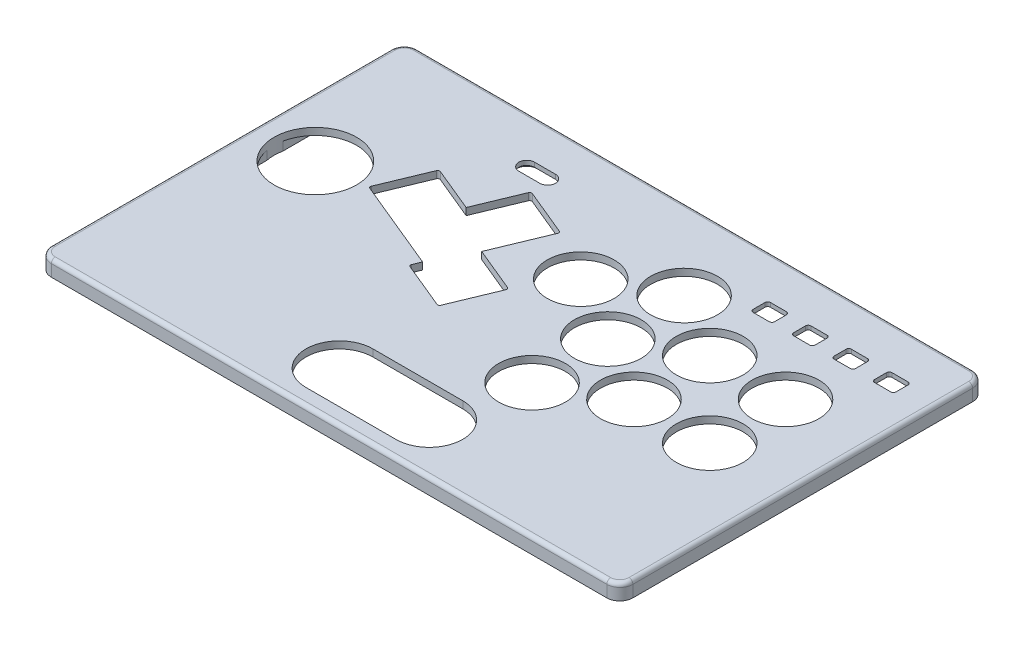
SolidWorks part; units mm, degrees
ref_plane "Front Plane" through (0, 0, 0) normal (0, 0, 1) x (1, 0, 0)
ref_plane "Top Plane" through (0, 0, 0) normal (0, 1, 0) x (1, 0, 0)
ref_plane "Right Plane" through (0, 0, 0) normal (1, 0, 0) x (0, 0, -1)
sketch "Sketch1" plane through (0, 0, 0) normal (0, 1, 0) x (1, 0, 0)
  line L1 (0, 0) -> (222.53, 0)
  line L2 (0, 0) -> (0, 140)
  line L3 (0, 140) -> (222.53, 140)
  line L4 (222.53, 0) -> (222.53, 140)
  line L5 (217.53, 140) -> (50.88, 140) construction
  line L6 (222.53, 5) -> (222.53, 135) construction
extrude "Top Plate" add sketch "Sketch1" along normal blind 6
fillet "Corner Fillet" radius 5 4 edges at (0, 3, -140) (0, 3, 0) (222.53, 3, -140) (222.53, 3, 0)
fillet "Top Fillet" radius 1.5 8 edges at (1.4645, 6, -1.4645) (0, 6, -70) (1.4645, 6, -138.5355) (111.265, 6, -140) (221.0655, 6, -138.5355) (222.53, 6, -70) (221.0655, 6, -1.4645) (111.265, 6, 0)
hole_wizard "M3 Clearance Hole1" positions "3DSketch1" profile "Sketch3" hole size "M3" standard "ANSI Metric"
sketch3d "3DSketch1"
  line L0 (5, 0, 0) -> (217.53, 0, 0) construction
  line L1 (222.53, 0, -5) -> (222.53, 0, -135) construction
  line L2 (217.53, 0, -140) -> (5, 0, -140) construction
  line L3 (0, 0, -135) -> (0, 0, -5) construction
  point P0 (217.03, 0, -5.5)
  point P2 (217.03, 0, -134.5)
  point P4 (5.5, 0, -134.5)
  point P6 (5.5, 0, -5.5)
  dimension "D1" = 5.5
  dimension "D2" = 5.5
  dimension "D3" = 5.5
  dimension "D4" = 5.5
  dimension "D5" = 5.5
  dimension "D6" = 5.5
  dimension "D7" = 5.5
  dimension "D8" = 5.5
sketch "Sketch3" plane through (217.03, 0, -5.5) normal (1, 0, 0) x (0, 0, -1)
  line L0 (0, 0) -> (0, 5.25)
  line L1 (0, 5.25) -> (1.7, 4.2285)
  line L2 (1.7, 4.2285) -> (1.7, 0)
  line L5 (1.7, 0) -> (0, 0)
  line L10 (0, 5.25) -> (-1.7, 4.2285) construction
  line L11 (0, -6.35) -> (0, 107.95) construction
  dimension "Hole Dia." = 3.4
  dimension "Hole Depth" = 5.25
  dimension "Drill Angle" = 118
sketch "Sketch4" plane through (0, 6, 0) normal (0, -1, 0) x (-1, 0, 0)
  line L0 (-94.0588, 59.555) -> (-76.4589, 66.8451) construction
  line L1 (-94.0588, 59.555) -> (-101.349, 77.1549) construction
  line L2 (-76.4589, 66.8451) -> (-77.9897, 70.5406) construction
  line L3 (-101.349, 77.1549) -> (-83.7491, 84.445) construction
  line L4 (-94.0588, 59.555) -> (-83.7491, 84.445) construction
  line L5 (-76.4589, 66.8451) -> (-101.349, 77.1549) construction
  line L6 (-77.9897, 70.5406) -> (-60.3898, 77.8307) construction
  line L7 (-83.7491, 84.445) -> (-85.2798, 88.1405) construction
  line L8 (-60.3898, 77.8307) -> (-67.6799, 95.4306) construction
  line L9 (-85.2798, 88.1405) -> (-67.6799, 95.4306) construction
  line L10 (-77.9897, 70.5406) -> (-67.6799, 95.4306) construction
  line L11 (-60.3898, 77.8307) -> (-85.2798, 88.1405) construction
  line L12 (-60.3898, 77.8307) -> (-42.7899, 85.1209) construction
  line L14 (-42.7899, 85.1209) -> (-50.08, 102.7208) construction
  line L15 (-67.6799, 95.4306) -> (-50.08, 102.7208) construction
  line L16 (-60.3898, 77.8307) -> (-50.08, 102.7208) construction
  line L17 (-42.7899, 85.1209) -> (-67.6799, 95.4306) construction
  line L19 (-67.6799, 95.4306) -> (-74.97, 113.0306) construction
  line L20 (-85.2798, 88.1405) -> (-92.5699, 105.7404) construction
  line L21 (-74.97, 113.0306) -> (-92.5699, 105.7404) construction
  line L22 (-67.6799, 95.4306) -> (-92.5699, 105.7404) construction
  line L23 (-85.2798, 88.1405) -> (-74.97, 113.0306) construction
  line L24 (-5, 0) -> (-217.53, 0) construction
  line L25 (-60.0836, 77.0916) -> (-42.4837, 84.3818)
  line L26 (-42.0508, 85.427) -> (-49.3409, 103.0269)
  line L27 (-67.2469, 96.4759) -> (-50.3861, 103.4599)
  line L28 (-67.2469, 96.4759) -> (-74.2309, 113.3367)
  line L29 (-75.2761, 113.7697) -> (-92.876, 106.4795)
  line L30 (-86.0189, 87.8344) -> (-93.309, 105.4343)
  line L31 (-84.7943, 84.878) -> (-86.0189, 87.8344)
  line L32 (-101.6551, 77.894) -> (-84.7943, 84.878)
  line L33 (-94.7979, 59.2488) -> (-102.0881, 76.8487)
  line L34 (-93.7527, 58.8159) -> (-76.1528, 66.106)
  line L35 (-75.7198, 67.1513) -> (-76.9444, 70.1077)
  line L36 (-76.9444, 70.1077) -> (-60.0836, 77.0916)
  line L37 (-66.9408, 95.7368) -> (-74.537, 114.0758) construction
  line L38 (-67.986, 96.1698) -> (-49.647, 103.766) construction
  line L39 (-74.537, 114.0758) -> (-93.6152, 106.1734) construction
  line L40 (-86.0189, 87.8344) -> (-93.6152, 106.1734) construction
  line L41 (-102.3942, 77.5878) -> (-84.7943, 84.878) construction
  line L42 (-94.4918, 58.5097) -> (-102.3942, 77.5878) construction
  line L43 (-94.4918, 58.5097) -> (-75.4137, 66.4122) construction
  line L44 (-75.4137, 66.4122) -> (-76.9444, 70.1077) construction
  line L45 (-60.0836, 77.0916) -> (-41.7446, 84.6879) construction
  line L46 (-41.7446, 84.6879) -> (-49.647, 103.766) construction
  line L47 (-130.64, 18.99) -> (-96.24, 18.99) construction
  line L48 (-130.64, 31.79) -> (-96.24, 31.79)
  line L49 (-130.64, 6.19) -> (-96.24, 6.19)
  circle A0 centre (-23, 83.0083) radius 15.8
  circle A1 centre (-137.9339, 51) radius 12.8
  circle A2 centre (-162.9339, 65) radius 12.8
  circle A3 centre (-191.9339, 65) radius 12.8
  circle A4 centre (-191.9339, 94) radius 12.8
  circle A5 centre (-162.9339, 94) radius 12.8
  circle A6 centre (-137.9339, 80) radius 12.8
  circle A7 centre (-138.1143, 108.9994) radius 12.8
  circle A8 centre (-112.9159, 94.6459) radius 12.8
  arc A9 (-92.876, 106.4795) -> (-93.309, 105.4343) centre (-92.5699, 105.7404) ccw
  arc A10 (-101.6551, 77.894) -> (-102.0881, 76.8487) centre (-101.349, 77.1549) ccw
  arc A11 (-94.7979, 59.2488) -> (-93.7527, 58.8159) centre (-94.0588, 59.555) ccw
  arc A12 (-76.1528, 66.106) -> (-75.7198, 67.1513) centre (-76.4589, 66.8451) ccw
  arc A13 (-42.4837, 84.3818) -> (-42.0508, 85.427) centre (-42.7899, 85.1209) ccw
  arc A14 (-74.2309, 113.3367) -> (-75.2761, 113.7697) centre (-74.97, 113.0306) ccw
  arc A15 (-49.3409, 103.0269) -> (-50.3861, 103.4599) centre (-50.08, 102.7208) ccw
  arc A16 (-130.64, 31.79) -> (-130.64, 6.19) centre (-130.64, 18.99) ccw
  arc A17 (-96.24, 6.19) -> (-96.24, 31.79) centre (-96.24, 18.99) ccw
  point P2 (-23, 83.0083)
  point P5 (0, 0)
  point P28 (-88.9039, 72)
  point P29 (-72.8348, 82.9856)
  point P30 (-55.2349, 90.2758)
  point P35 (-80.1249, 100.5855)
  point P90 (-113.44, 18.99)
  point P96 (-83.44, 18.99)
  point P97 (-143.44, 18.99)
  point P98 (-191.9339, 94)
  point P100 (-162.9339, 94)
  point P102 (-191.9339, 65)
  point P104 (-162.9339, 65)
  point P106 (-138.1143, 108.9994)
  point P108 (-137.9339, 80)
  point P110 (-137.9339, 51)
  point P112 (-112.9159, 94.6459)
  point P114 (-113.44, 18.99)
  point P116 (-80.1249, 100.5855)
  point P118 (-88.9039, 72)
  point P120 (-72.8348, 82.9856)
  point P122 (0, 0)
  dimension "D1" = 31.6
  dimension "D2" = 25.6
  dimension "D6" = 0.8
  dimension "D8" = 12.8
  dimension "D3" = 22.5
  dimension "D4" = 19.05
  dimension "D5" = 0.8
  dimension "D7" = 60
extrude "Primary Buttons" cut sketch "Sketch4" along normal blind 10 contours A15 L26 A13 L25 L36 L35 A12 L34 A11 L33 A10 L32 L31 L30 A9 L29 A14 L28 L27 | A0 | A8 | A7 | A5 | A4 | A6 | A1 | A2 | A3 | A17 L49 A16 L48 region at (74.3293, 6, -86.4969) region at (113.44, 6, -18.99) region at (23, 6, -83.0083) region at (137.9339, 6, -51) region at (162.9339, 6, -65) region at (191.9339, 6, -65) region at (191.9339, 6, -94) region at (162.9339, 6, -94) region at (137.9339, 6, -80) region at (138.1143, 6, -108.9994) region at (112.9159, 6, -94.6459)
sketch "Sketch5" plane through (0, 0, 0) normal (0, -1, 0) x (1, 0, 0)
  line L2 (155.9, -122.22) -> (155.9, -117.62)
  line L3 (156.9, -116.62) -> (163.1, -116.62)
  line L4 (164.1, -122.22) -> (164.1, -117.62)
  line L5 (155.9, -123.22) -> (164.1, -116.62) construction
  line L6 (155.9, -116.62) -> (164.1, -123.22) construction
  line L7 (156.9, -123.22) -> (163.1, -123.22)
  line L8 (171.4, -122.22) -> (171.4, -117.62)
  line L9 (172.4, -116.62) -> (178.6, -116.62)
  line L10 (179.6, -122.22) -> (179.6, -117.62)
  line L11 (172.4, -123.22) -> (178.6, -123.22)
  line L12 (171.4, -123.22) -> (179.6, -116.62) construction
  line L13 (171.4, -116.62) -> (179.6, -123.22) construction
  line L14 (186.9, -122.22) -> (186.9, -117.62)
  line L15 (187.9, -116.62) -> (194.1, -116.62)
  line L16 (195.1, -122.22) -> (195.1, -117.62)
  line L17 (187.9, -123.22) -> (194.1, -123.22)
  line L18 (186.9, -123.22) -> (195.1, -116.62) construction
  line L19 (186.9, -116.62) -> (195.1, -123.22) construction
  line L20 (202.4, -122.22) -> (202.4, -117.62)
  line L21 (203.4, -116.62) -> (209.6, -116.62)
  line L22 (210.6, -122.22) -> (210.6, -117.62)
  line L23 (203.4, -123.22) -> (209.6, -123.22)
  line L24 (202.4, -123.22) -> (210.6, -116.62) construction
  line L25 (202.4, -116.62) -> (210.6, -123.22) construction
  arc A0 (163.1, -123.22) -> (164.1, -122.22) centre (163.1, -122.22) ccw
  arc A1 (156.9, -123.22) -> (155.9, -122.22) centre (156.9, -122.22) cw
  arc A2 (155.9, -117.62) -> (156.9, -116.62) centre (156.9, -117.62) cw
  arc A3 (163.1, -116.62) -> (164.1, -117.62) centre (163.1, -117.62) cw
  arc A4 (178.6, -123.22) -> (179.6, -122.22) centre (178.6, -122.22) ccw
  arc A5 (172.4, -123.22) -> (171.4, -122.22) centre (172.4, -122.22) cw
  arc A6 (171.4, -117.62) -> (172.4, -116.62) centre (172.4, -117.62) cw
  arc A7 (178.6, -116.62) -> (179.6, -117.62) centre (178.6, -117.62) cw
  arc A8 (194.1, -123.22) -> (195.1, -122.22) centre (194.1, -122.22) ccw
  arc A9 (187.9, -123.22) -> (186.9, -122.22) centre (187.9, -122.22) cw
  arc A10 (186.9, -117.62) -> (187.9, -116.62) centre (187.9, -117.62) cw
  arc A11 (194.1, -116.62) -> (195.1, -117.62) centre (194.1, -117.62) cw
  arc A12 (209.6, -123.22) -> (210.6, -122.22) centre (209.6, -122.22) ccw
  arc A13 (203.4, -123.22) -> (202.4, -122.22) centre (203.4, -122.22) cw
  arc A14 (202.4, -117.62) -> (203.4, -116.62) centre (203.4, -117.62) cw
  arc A15 (209.6, -116.62) -> (210.6, -117.62) centre (209.6, -117.62) cw
  point P0 (160, -119.92)
  point P6 (160, -119.92)
  point P7 (175.5, -119.92)
  point P39 (191, -119.92)
  point P56 (206.5, -119.92)
  dimension "D1" = 6.6
  dimension "D3" = 1
  dimension "D2" = 8.2
  dimension "D5" = 15.5
  dimension "D4" = 4
extrude "Extra Buttons" cut sketch "Sketch5" against normal up to next
sketch "Sketch8" plane through (0, 0, 0) normal (0, -1, 0) x (1, 0, 0)
  line L24 (215.03, -132.5) -> (215.03, -7.5)
  line L25 (7.5, -132.5) -> (215.03, -132.5)
  line L26 (7.5, -7.5) -> (7.5, -132.5)
  line L27 (215.03, -7.5) -> (7.5, -7.5)
  line L28 (215.03, -132.5) -> (215.03, -7.5)
  line L29 (7.5, -132.5) -> (215.03, -132.5)
  line L30 (7.5, -7.5) -> (7.5, -132.5)
  line L31 (215.03, -7.5) -> (7.5, -7.5)
  dimension "D1" = 7.5
extrude "Hollow Out" cut sketch "Sketch8" against normal blind 3.3
fillet "Fillet1" radius 10 3 edges at (7.5, 1.65, -132.5) (7.5, 1.65, -7.5) (215.03, 1.65, -7.5)
fillet "Fillet2" radius 5 1 edges at (215.03, 1.65, -132.5)
sketch "Sketch6" plane through (0, 3.3, 0) normal (0, -1, 0) x (1, 0, 0)
  line L1 (152, -127.92) -> (214.5, -127.92)
  line L2 (152, -127.92) -> (152, -111.92)
  line L3 (152, -111.92) -> (214.5, -111.92)
  line L4 (214.5, -127.92) -> (214.5, -111.92)
  line L5 (203.4, -116.62) -> (209.6, -116.62) construction
  line L6 (155.9, -122.22) -> (155.9, -117.62) construction
  point P11 (206.5, -116.62)
  point P12 (155.9, -119.92)
  dimension "D1" = 8
  dimension "D2" = 8
  dimension "D3" = 8
  dimension "D4" = 8
extrude "Extra Button Keyswitch Relief" cut sketch "Sketch6" against normal blind 1.1
sketch "Sketch9" plane through (0, 6, 0) normal (0, 1, 0) x (1, 0, 0)
  line L0 (68.635, 121.5875) -> (69.975, 121.5875) construction
  line L3 (65.305, 121.5875) -> (73.305, 121.5875) construction
  line L4 (65.305, 124.5875) -> (73.305, 124.5875)
  line L5 (65.305, 118.5875) -> (73.305, 118.5875)
  line L6 (69.975, 121.0025) -> (69.975, 122.1725) construction
  line L7 (68.635, 121.0025) -> (68.635, 122.1725) construction
  arc A0 (65.305, 124.5875) -> (65.305, 118.5875) centre (65.305, 121.5875) ccw
  arc A1 (73.305, 118.5875) -> (73.305, 124.5875) centre (73.305, 121.5875) ccw
  point P3 (69.975, 121.5875)
  point P6 (68.635, 121.5875)
  point P8 (69.305, 121.5875)
  dimension "D2" = 3
  dimension "D1" = 8
extrude "Light Guide Cutout" cut sketch "Sketch9" against normal blind 10
chamfer "Chamfer1" distance 1 angle 45 4 edges at (76.305, 3.3, -121.5875) (69.305, 3.3, -118.5875) (62.305, 3.3, -121.5875) (69.305, 3.3, -124.5875)
sketch "Sketch10" plane through (49.38, 0, 0) normal (-1, 0, 0) x (0, 0, 1)
  line L0 (-132.5, 0) -> (-132.5, 3.3)
  line L1 (-132.5, 3.3) -> (-127.5, 3.3)
  line L2 (-111.92, 3.3) -> (-127.92, 3.3) construction
  line L3 (-127.5, -3.2) -> (-127.5, -6.2)
  line L4 (-127.5, -6.2) -> (-122.5, -6.2)
  line L5 (-122.5, -6.2) -> (-122.5, 3.3)
  line L6 (-122.5, 3.3) -> (-127.5, 3.3)
  line L7 (-132.5, 0) -> (-127.5, -3.2)
  dimension "D1" = 9.5
  dimension "D2" = 5
  dimension "D3" = 5
  dimension "D4" = 3
  dimension "D5" = 5
extrude "Boss-Extrude1" add sketch "Sketch10" along normal blind 12 from offset 4
